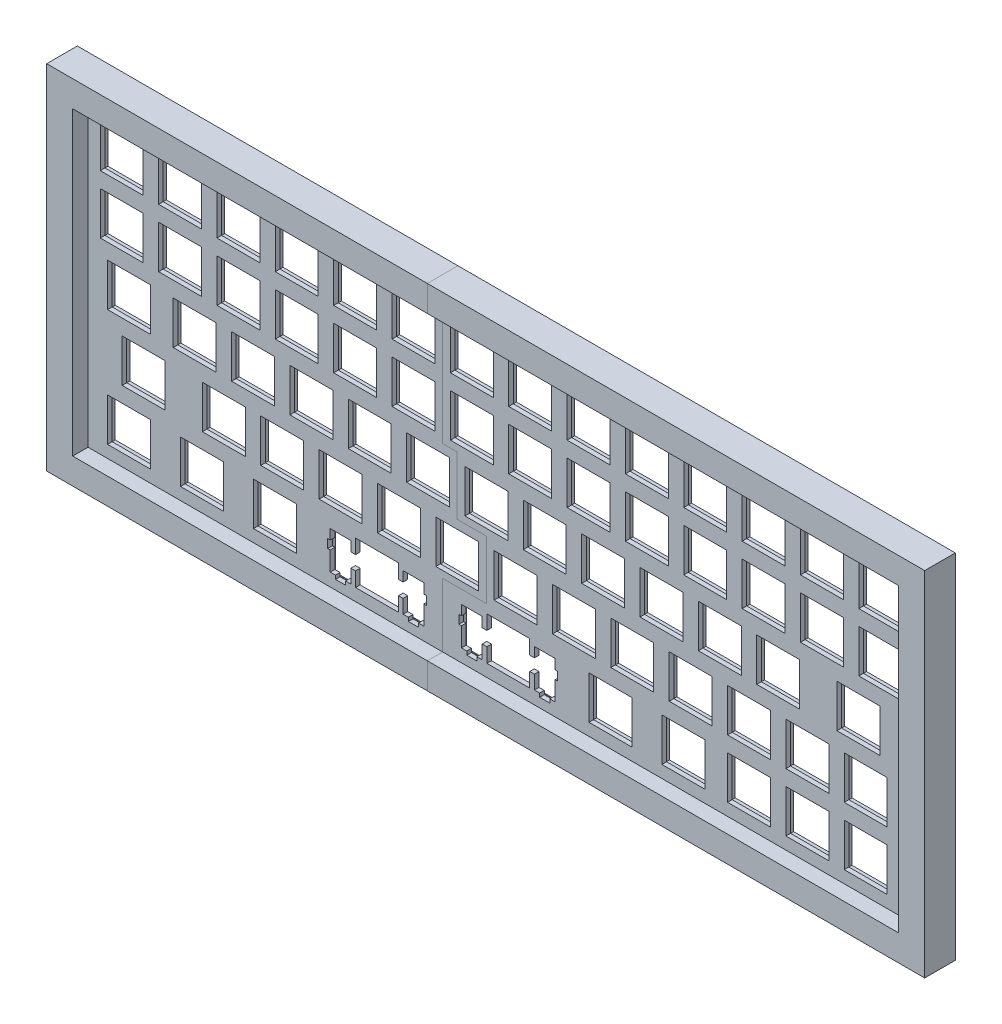
SolidWorks part; units mm, degrees
ref_plane "Front Plane" through (0, 0, 0) normal (0, 0, 1) x (1, 0, 0)
ref_plane "Top Plane" through (0, 0, 0) normal (0, 1, 0) x (1, 0, 0)
ref_plane "Right Plane" through (0, 0, 0) normal (1, 0, 0) x (0, 0, -1)
sketch "Model" plane through (0, 0, 0) normal (0, 0, 1) x (1, 0, 0)
  line L0 (0.0951, 95.5123) -> (266.8083, 95.5123)
  line L1 (266.8083, 95.5123) -> (266.8083, 0.2577)
  line L2 (266.8083, 0.2577) -> (0.0951, 0.2577)
  line L3 (0.0951, 0.2577) -> (0.0951, 95.5123)
  line L4 (85.9664, 16.7839) -> (85.9664, 12.0832)
  line L5 (85.9664, 12.0832) -> (84.4423, 12.0832)
  line L6 (84.4423, 12.0832) -> (84.4423, 15.3136)
  line L7 (84.4423, 15.3136) -> (77.6909, 15.3136)
  line L8 (77.6909, 15.3136) -> (77.6909, 12.0832)
  line L9 (77.6909, 12.0832) -> (76.8667, 12.0832)
  line L10 (76.8667, 12.0832) -> (76.8667, 9.2843)
  line L11 (76.8667, 9.2843) -> (77.6909, 9.2843)
  line L12 (77.6909, 9.2843) -> (77.6909, 3.0139)
  line L13 (77.6909, 3.0139) -> (79.416, 3.0139)
  line L14 (79.416, 3.0139) -> (79.416, 1.8136)
  line L15 (79.416, 1.8136) -> (82.7167, 1.8136)
  line L16 (82.7167, 1.8136) -> (82.7167, 3.0139)
  line L17 (82.7167, 3.0139) -> (84.4423, 3.0139)
  line L18 (84.4423, 3.0139) -> (84.4423, 7.4845)
  line L19 (84.4423, 7.4845) -> (85.9664, 7.4845)
  line L20 (85.9664, 7.4845) -> (85.9664, 2.7838)
  line L21 (85.9664, 2.7838) -> (99.9678, 2.7838)
  line L22 (99.9678, 2.7838) -> (99.9678, 7.4845)
  line L23 (99.9678, 7.4845) -> (101.4921, 7.4845)
  line L24 (101.4921, 7.4845) -> (101.4921, 3.0139)
  line L25 (101.4921, 3.0139) -> (103.2172, 3.0139)
  line L26 (103.2172, 3.0139) -> (103.2172, 1.8136)
  line L27 (103.2172, 1.8136) -> (106.5183, 1.8136)
  line L28 (106.5183, 1.8136) -> (106.5183, 3.0139)
  line L29 (106.5183, 3.0139) -> (108.2434, 3.0139)
  line L30 (108.2434, 3.0139) -> (108.2434, 9.2843)
  line L31 (108.2434, 9.2843) -> (109.0675, 9.2843)
  line L32 (109.0675, 9.2843) -> (109.0675, 12.0832)
  line L33 (109.0675, 12.0832) -> (108.2434, 12.0832)
  line L34 (108.2434, 12.0832) -> (108.2434, 15.3136)
  line L35 (108.2434, 15.3136) -> (101.4921, 15.3136)
  line L36 (101.4921, 15.3136) -> (101.4921, 12.0832)
  line L37 (101.4921, 12.0832) -> (99.9678, 12.0832)
  line L38 (99.9678, 12.0832) -> (99.9678, 16.7839)
  line L39 (99.9678, 16.7839) -> (85.9664, 16.7839)
  line L40 (128.8324, 16.7839) -> (128.8324, 12.0832)
  line L41 (128.8324, 12.0832) -> (127.3074, 12.0832)
  line L42 (127.3074, 12.0832) -> (127.3074, 15.3136)
  line L43 (127.3074, 15.3136) -> (120.557, 15.3136)
  line L44 (120.557, 15.3136) -> (120.557, 12.0832)
  line L45 (120.557, 12.0832) -> (119.731, 12.0832)
  line L46 (119.731, 12.0832) -> (119.731, 9.2843)
  line L47 (119.731, 9.2843) -> (120.557, 9.2843)
  line L48 (120.557, 9.2843) -> (120.557, 3.0139)
  line L49 (120.557, 3.0139) -> (122.2821, 3.0139)
  line L50 (122.2821, 3.0139) -> (122.2821, 1.8136)
  line L51 (122.2821, 1.8136) -> (125.5813, 1.8136)
  line L52 (125.5813, 1.8136) -> (125.5813, 3.0139)
  line L53 (125.5813, 3.0139) -> (127.3074, 3.0139)
  line L54 (127.3074, 3.0139) -> (127.3074, 7.4845)
  line L55 (127.3074, 7.4845) -> (128.8324, 7.4845)
  line L56 (128.8324, 7.4845) -> (128.8324, 2.7838)
  line L57 (128.8324, 2.7838) -> (142.8321, 2.7838)
  line L58 (142.8321, 2.7838) -> (142.8321, 7.4845)
  line L59 (142.8321, 7.4845) -> (144.3582, 7.4845)
  line L60 (144.3582, 7.4845) -> (144.3582, 3.0139)
  line L61 (144.3582, 3.0139) -> (146.0823, 3.0139)
  line L62 (146.0823, 3.0139) -> (146.0823, 1.8136)
  line L63 (146.0823, 1.8136) -> (149.3825, 1.8136)
  line L64 (149.3825, 1.8136) -> (149.3825, 3.0139)
  line L65 (149.3825, 3.0139) -> (151.1076, 3.0139)
  line L66 (151.1076, 3.0139) -> (151.1076, 9.2843)
  line L67 (151.1076, 9.2843) -> (151.9336, 9.2843)
  line L68 (151.9336, 9.2843) -> (151.9336, 12.0832)
  line L69 (151.9336, 12.0832) -> (151.1076, 12.0832)
  line L70 (151.1076, 12.0832) -> (151.1076, 15.3136)
  line L71 (151.1076, 15.3136) -> (144.3582, 15.3136)
  line L72 (144.3582, 15.3136) -> (144.3582, 12.0832)
  line L73 (144.3582, 12.0832) -> (142.8321, 12.0832)
  line L74 (142.8321, 12.0832) -> (142.8321, 16.7839)
  line L75 (142.8321, 16.7839) -> (128.8324, 16.7839)
  line L76 (5.0012, 16.7838) -> (19.0012, 16.7838)
  line L77 (19.0012, 16.7838) -> (19.0012, 2.7838)
  line L78 (19.0012, 2.7838) -> (5.0012, 2.7838)
  line L79 (5.0012, 2.7838) -> (5.0012, 16.7838)
  line L80 (28.8134, 16.7838) -> (42.8134, 16.7838)
  line L81 (42.8134, 16.7838) -> (42.8134, 2.7838)
  line L82 (42.8134, 2.7838) -> (28.8134, 2.7838)
  line L83 (28.8134, 2.7838) -> (28.8134, 16.7838)
  line L84 (52.6286, 16.7838) -> (66.6286, 16.7838)
  line L85 (66.6286, 16.7838) -> (66.6286, 2.7838)
  line L86 (66.6286, 2.7838) -> (52.6286, 2.7838)
  line L87 (52.6286, 2.7838) -> (52.6286, 16.7838)
  line L88 (162.1701, 16.7838) -> (176.1701, 16.7838)
  line L89 (176.1701, 16.7838) -> (176.1701, 2.7838)
  line L90 (176.1701, 2.7838) -> (162.1701, 2.7838)
  line L91 (162.1701, 2.7838) -> (162.1701, 16.7838)
  line L92 (185.9853, 16.7838) -> (199.9853, 16.7838)
  line L93 (199.9853, 16.7838) -> (199.9853, 2.7838)
  line L94 (199.9853, 2.7838) -> (185.9853, 2.7838)
  line L95 (185.9853, 2.7838) -> (185.9853, 16.7838)
  line L96 (207.4174, 16.7838) -> (221.4174, 16.7838)
  line L97 (221.4174, 16.7838) -> (221.4174, 2.7838)
  line L98 (221.4174, 2.7838) -> (207.4174, 2.7838)
  line L99 (207.4174, 2.7838) -> (207.4174, 16.7838)
  line L100 (226.4683, 16.7838) -> (240.4683, 16.7838)
  line L101 (240.4683, 16.7838) -> (240.4683, 2.7838)
  line L102 (240.4683, 2.7838) -> (226.4683, 2.7838)
  line L103 (226.4683, 2.7838) -> (226.4683, 16.7838)
  line L104 (245.5193, 16.7838) -> (259.5193, 16.7838)
  line L105 (259.5193, 16.7838) -> (259.5193, 2.7838)
  line L106 (259.5193, 2.7838) -> (245.5193, 2.7838)
  line L107 (245.5193, 2.7838) -> (245.5193, 16.7838)
  line L108 (9.7625, 35.8347) -> (23.7625, 35.8347)
  line L109 (23.7625, 35.8347) -> (23.7625, 21.8347)
  line L110 (23.7625, 21.8347) -> (9.7625, 21.8347)
  line L111 (9.7625, 21.8347) -> (9.7625, 35.8347)
  line L112 (35.959, 35.8347) -> (49.959, 35.8347)
  line L113 (49.959, 35.8347) -> (49.959, 21.8347)
  line L114 (49.959, 21.8347) -> (35.959, 21.8347)
  line L115 (35.959, 21.8347) -> (35.959, 35.8347)
  line L116 (55.01, 35.8347) -> (69.01, 35.8347)
  line L117 (69.01, 35.8347) -> (69.01, 21.8347)
  line L118 (69.01, 21.8347) -> (55.01, 21.8347)
  line L119 (55.01, 21.8347) -> (55.01, 35.8347)
  line L120 (74.0609, 35.8347) -> (88.0609, 35.8347)
  line L121 (88.0609, 35.8347) -> (88.0609, 21.8347)
  line L122 (88.0609, 21.8347) -> (74.0609, 21.8347)
  line L123 (74.0609, 21.8347) -> (74.0609, 35.8347)
  line L124 (93.1119, 35.8347) -> (107.1119, 35.8347)
  line L125 (107.1119, 35.8347) -> (107.1119, 21.8347)
  line L126 (107.1119, 21.8347) -> (93.1119, 21.8347)
  line L127 (93.1119, 21.8347) -> (93.1119, 35.8347)
  line L128 (112.1626, 35.8347) -> (126.1626, 35.8347)
  line L129 (126.1626, 35.8347) -> (126.1626, 21.8347)
  line L130 (126.1626, 21.8347) -> (112.1626, 21.8347)
  line L131 (112.1626, 21.8347) -> (112.1626, 35.8347)
  line L132 (131.2136, 35.8347) -> (145.2136, 35.8347)
  line L133 (145.2136, 35.8347) -> (145.2136, 21.8347)
  line L134 (145.2136, 21.8347) -> (131.2136, 21.8347)
  line L135 (131.2136, 21.8347) -> (131.2136, 35.8347)
  line L136 (150.2645, 35.8347) -> (164.2645, 35.8347)
  line L137 (164.2645, 35.8347) -> (164.2645, 21.8347)
  line L138 (164.2645, 21.8347) -> (150.2645, 21.8347)
  line L139 (150.2645, 21.8347) -> (150.2645, 35.8347)
  line L140 (169.3155, 35.8347) -> (183.3155, 35.8347)
  line L141 (183.3155, 35.8347) -> (183.3155, 21.8347)
  line L142 (183.3155, 21.8347) -> (169.3155, 21.8347)
  line L143 (169.3155, 21.8347) -> (169.3155, 35.8347)
  line L144 (188.3664, 35.8347) -> (202.3664, 35.8347)
  line L145 (202.3664, 35.8347) -> (202.3664, 21.8347)
  line L146 (202.3664, 21.8347) -> (188.3664, 21.8347)
  line L147 (188.3664, 21.8347) -> (188.3664, 35.8347)
  line L148 (207.4174, 35.8347) -> (221.4174, 35.8347)
  line L149 (221.4174, 35.8347) -> (221.4174, 21.8347)
  line L150 (221.4174, 21.8347) -> (207.4174, 21.8347)
  line L151 (207.4174, 21.8347) -> (207.4174, 35.8347)
  line L152 (226.4683, 35.8347) -> (240.4683, 35.8347)
  line L153 (240.4683, 35.8347) -> (240.4683, 21.8347)
  line L154 (240.4683, 21.8347) -> (226.4683, 21.8347)
  line L155 (226.4683, 21.8347) -> (226.4683, 35.8347)
  line L156 (245.5193, 35.8347) -> (259.5193, 35.8347)
  line L157 (259.5193, 35.8347) -> (259.5193, 21.8347)
  line L158 (259.5193, 21.8347) -> (245.5193, 21.8347)
  line L159 (245.5193, 21.8347) -> (245.5193, 35.8347)
  line L160 (5.0012, 54.8858) -> (19.0012, 54.8858)
  line L161 (19.0012, 54.8858) -> (19.0012, 40.8858)
  line L162 (19.0012, 40.8858) -> (5.0012, 40.8858)
  line L163 (5.0012, 40.8858) -> (5.0012, 54.8858)
  line L164 (26.4335, 54.8858) -> (40.4335, 54.8858)
  line L165 (40.4335, 54.8858) -> (40.4335, 40.8858)
  line L166 (40.4335, 40.8858) -> (26.4335, 40.8858)
  line L167 (26.4335, 40.8858) -> (26.4335, 54.8858)
  line L168 (45.4845, 54.8858) -> (59.4845, 54.8858)
  line L169 (59.4845, 54.8858) -> (59.4845, 40.8858)
  line L170 (59.4845, 40.8858) -> (45.4845, 40.8858)
  line L171 (45.4845, 40.8858) -> (45.4845, 54.8858)
  line L172 (64.5354, 54.8858) -> (78.5354, 54.8858)
  line L173 (78.5354, 54.8858) -> (78.5354, 40.8858)
  line L174 (78.5354, 40.8858) -> (64.5354, 40.8858)
  line L175 (64.5354, 40.8858) -> (64.5354, 54.8858)
  line L176 (83.5864, 54.8858) -> (97.5864, 54.8858)
  line L177 (97.5864, 54.8858) -> (97.5864, 40.8858)
  line L178 (97.5864, 40.8858) -> (83.5864, 40.8858)
  line L179 (83.5864, 40.8858) -> (83.5864, 54.8858)
  line L180 (102.6371, 54.8858) -> (116.6371, 54.8858)
  line L181 (116.6371, 54.8858) -> (116.6371, 40.8858)
  line L182 (116.6371, 40.8858) -> (102.6371, 40.8858)
  line L183 (102.6371, 40.8858) -> (102.6371, 54.8858)
  line L184 (121.6881, 54.8858) -> (135.6881, 54.8858)
  line L185 (135.6881, 54.8858) -> (135.6881, 40.8858)
  line L186 (135.6881, 40.8858) -> (121.6881, 40.8858)
  line L187 (121.6881, 40.8858) -> (121.6881, 54.8858)
  line L188 (140.739, 54.8858) -> (154.739, 54.8858)
  line L189 (154.739, 54.8858) -> (154.739, 40.8858)
  line L190 (154.739, 40.8858) -> (140.739, 40.8858)
  line L191 (140.739, 40.8858) -> (140.739, 54.8858)
  line L192 (159.79, 54.8858) -> (173.79, 54.8858)
  line L193 (173.79, 54.8858) -> (173.79, 40.8858)
  line L194 (173.79, 40.8858) -> (159.79, 40.8858)
  line L195 (159.79, 40.8858) -> (159.79, 54.8858)
  line L196 (178.8409, 54.8858) -> (192.8409, 54.8858)
  line L197 (192.8409, 54.8858) -> (192.8409, 40.8858)
  line L198 (192.8409, 40.8858) -> (178.8409, 40.8858)
  line L199 (178.8409, 40.8858) -> (178.8409, 54.8858)
  line L200 (197.8919, 54.8858) -> (211.8919, 54.8858)
  line L201 (211.8919, 54.8858) -> (211.8919, 40.8858)
  line L202 (211.8919, 40.8858) -> (197.8919, 40.8858)
  line L203 (197.8919, 40.8858) -> (197.8919, 54.8858)
  line L204 (216.9428, 54.8858) -> (230.9428, 54.8858)
  line L205 (230.9428, 54.8858) -> (230.9428, 40.8858)
  line L206 (230.9428, 40.8858) -> (216.9428, 40.8858)
  line L207 (216.9428, 40.8858) -> (216.9428, 54.8858)
  line L208 (243.1382, 54.8858) -> (257.1382, 54.8858)
  line L209 (257.1382, 54.8858) -> (257.1382, 40.8858)
  line L210 (257.1382, 40.8858) -> (243.1382, 40.8858)
  line L211 (243.1382, 40.8858) -> (243.1382, 54.8858)
  line L212 (2.6198, 73.9368) -> (16.6198, 73.9368)
  line L213 (16.6198, 73.9368) -> (16.6198, 59.9368)
  line L214 (16.6198, 59.9368) -> (2.6198, 59.9368)
  line L215 (2.6198, 59.9368) -> (2.6198, 73.9368)
  line L216 (21.6708, 73.9368) -> (35.6708, 73.9368)
  line L217 (35.6708, 73.9368) -> (35.6708, 59.9368)
  line L218 (35.6708, 59.9368) -> (21.6708, 59.9368)
  line L219 (21.6708, 59.9368) -> (21.6708, 73.9368)
  line L220 (40.7217, 73.9368) -> (54.7217, 73.9368)
  line L221 (54.7217, 73.9368) -> (54.7217, 59.9368)
  line L222 (54.7217, 59.9368) -> (40.7217, 59.9368)
  line L223 (40.7217, 59.9368) -> (40.7217, 73.9368)
  line L224 (59.7727, 73.9368) -> (73.7727, 73.9368)
  line L225 (73.7727, 73.9368) -> (73.7727, 59.9368)
  line L226 (73.7727, 59.9368) -> (59.7727, 59.9368)
  line L227 (59.7727, 59.9368) -> (59.7727, 73.9368)
  line L228 (78.8236, 73.9368) -> (92.8236, 73.9368)
  line L229 (92.8236, 73.9368) -> (92.8236, 59.9368)
  line L230 (92.8236, 59.9368) -> (78.8236, 59.9368)
  line L231 (78.8236, 59.9368) -> (78.8236, 73.9368)
  line L232 (97.8732, 73.9368) -> (111.8732, 73.9368)
  line L233 (111.8732, 73.9368) -> (111.8732, 59.9368)
  line L234 (111.8732, 59.9368) -> (97.8732, 59.9368)
  line L235 (97.8732, 59.9368) -> (97.8732, 73.9368)
  line L236 (116.9238, 73.9368) -> (130.9238, 73.9368)
  line L237 (130.9238, 73.9368) -> (130.9238, 59.9368)
  line L238 (130.9238, 59.9368) -> (116.9238, 59.9368)
  line L239 (116.9238, 59.9368) -> (116.9238, 73.9368)
  line L240 (135.9768, 73.9368) -> (149.9768, 73.9368)
  line L241 (149.9768, 73.9368) -> (149.9768, 59.9368)
  line L242 (149.9768, 59.9368) -> (135.9768, 59.9368)
  line L243 (135.9768, 59.9368) -> (135.9768, 73.9368)
  line L244 (155.0278, 73.9368) -> (169.0278, 73.9368)
  line L245 (169.0278, 73.9368) -> (169.0278, 59.9368)
  line L246 (169.0278, 59.9368) -> (155.0278, 59.9368)
  line L247 (155.0278, 59.9368) -> (155.0278, 73.9368)
  line L248 (174.0787, 73.9368) -> (188.0787, 73.9368)
  line L249 (188.0787, 73.9368) -> (188.0787, 59.9368)
  line L250 (188.0787, 59.9368) -> (174.0787, 59.9368)
  line L251 (174.0787, 59.9368) -> (174.0787, 73.9368)
  line L252 (193.1297, 73.9368) -> (207.1297, 73.9368)
  line L253 (207.1297, 73.9368) -> (207.1297, 59.9368)
  line L254 (207.1297, 59.9368) -> (193.1297, 59.9368)
  line L255 (193.1297, 59.9368) -> (193.1297, 73.9368)
  line L256 (212.1806, 73.9368) -> (226.1806, 73.9368)
  line L257 (226.1806, 73.9368) -> (226.1806, 59.9368)
  line L258 (226.1806, 59.9368) -> (212.1806, 59.9368)
  line L259 (212.1806, 59.9368) -> (212.1806, 73.9368)
  line L260 (231.2316, 73.9368) -> (245.2316, 73.9368)
  line L261 (245.2316, 73.9368) -> (245.2316, 59.9368)
  line L262 (245.2316, 59.9368) -> (231.2316, 59.9368)
  line L263 (231.2316, 59.9368) -> (231.2316, 73.9368)
  line L264 (250.2825, 73.9368) -> (264.2825, 73.9368)
  line L265 (264.2825, 73.9368) -> (264.2825, 59.9368)
  line L266 (264.2825, 59.9368) -> (250.2825, 59.9368)
  line L267 (250.2825, 59.9368) -> (250.2825, 73.9368)
  line L268 (2.6198, 92.9877) -> (16.6198, 92.9877)
  line L269 (16.6198, 92.9877) -> (16.6198, 78.9877)
  line L270 (16.6198, 78.9877) -> (2.6198, 78.9877)
  line L271 (2.6198, 78.9877) -> (2.6198, 92.9877)
  line L272 (21.6708, 92.9877) -> (35.6708, 92.9877)
  line L273 (35.6708, 92.9877) -> (35.6708, 78.9877)
  line L274 (35.6708, 78.9877) -> (21.6708, 78.9877)
  line L275 (21.6708, 78.9877) -> (21.6708, 92.9877)
  line L276 (40.7217, 92.9877) -> (54.7217, 92.9877)
  line L277 (54.7217, 92.9877) -> (54.7217, 78.9877)
  line L278 (54.7217, 78.9877) -> (40.7217, 78.9877)
  line L279 (40.7217, 78.9877) -> (40.7217, 92.9877)
  line L280 (59.7727, 92.9877) -> (73.7727, 92.9877)
  line L281 (73.7727, 92.9877) -> (73.7727, 78.9877)
  line L282 (73.7727, 78.9877) -> (59.7727, 78.9877)
  line L283 (59.7727, 78.9877) -> (59.7727, 92.9877)
  line L284 (78.8236, 92.9877) -> (92.8236, 92.9877)
  line L285 (92.8236, 92.9877) -> (92.8236, 78.9877)
  line L286 (92.8236, 78.9877) -> (78.8236, 78.9877)
  line L287 (78.8236, 78.9877) -> (78.8236, 92.9877)
  line L288 (97.8732, 92.9877) -> (111.8732, 92.9877)
  line L289 (111.8732, 92.9877) -> (111.8732, 78.9877)
  line L290 (111.8732, 78.9877) -> (97.8732, 78.9877)
  line L291 (97.8732, 78.9877) -> (97.8732, 92.9877)
  line L292 (116.9238, 92.9877) -> (130.9238, 92.9877)
  line L293 (130.9238, 92.9877) -> (130.9238, 78.9877)
  line L294 (130.9238, 78.9877) -> (116.9238, 78.9877)
  line L295 (116.9238, 78.9877) -> (116.9238, 92.9877)
  line L296 (135.9768, 92.9877) -> (149.9768, 92.9877)
  line L297 (149.9768, 92.9877) -> (149.9768, 78.9877)
  line L298 (149.9768, 78.9877) -> (135.9768, 78.9877)
  line L299 (135.9768, 78.9877) -> (135.9768, 92.9877)
  line L300 (155.0278, 92.9877) -> (169.0278, 92.9877)
  line L301 (169.0278, 92.9877) -> (169.0278, 78.9877)
  line L302 (169.0278, 78.9877) -> (155.0278, 78.9877)
  line L303 (155.0278, 78.9877) -> (155.0278, 92.9877)
  line L304 (174.0787, 92.9877) -> (188.0787, 92.9877)
  line L305 (188.0787, 92.9877) -> (188.0787, 78.9877)
  line L306 (188.0787, 78.9877) -> (174.0787, 78.9877)
  line L307 (174.0787, 78.9877) -> (174.0787, 92.9877)
  line L308 (193.1297, 92.9877) -> (207.1297, 92.9877)
  line L309 (207.1297, 92.9877) -> (207.1297, 78.9877)
  line L310 (207.1297, 78.9877) -> (193.1297, 78.9877)
  line L311 (193.1297, 78.9877) -> (193.1297, 92.9877)
  line L312 (212.1806, 92.9877) -> (226.1806, 92.9877)
  line L313 (226.1806, 92.9877) -> (226.1806, 78.9877)
  line L314 (226.1806, 78.9877) -> (212.1806, 78.9877)
  line L315 (212.1806, 78.9877) -> (212.1806, 92.9877)
  line L316 (231.2316, 92.9877) -> (245.2316, 92.9877)
  line L317 (245.2316, 92.9877) -> (245.2316, 78.9877)
  line L318 (245.2316, 78.9877) -> (231.2316, 78.9877)
  line L319 (231.2316, 78.9877) -> (231.2316, 92.9877)
  line L320 (250.2825, 92.9877) -> (264.2825, 92.9877)
  line L321 (264.2825, 92.9877) -> (264.2825, 78.9877)
  line L322 (264.2825, 78.9877) -> (250.2825, 78.9877)
  line L323 (250.2825, 78.9877) -> (250.2825, 92.9877)
  dimension "D1" = 14
  dimension "D2" = 13.9997
  dimension "D3" = 5.051
  dimension "D4" = 5.051
extrude "Boss-Extrude1" add sketch "Model" along normal blind 1.5
sketch "Sketch2" plane through (0, 0, 1.5) normal (0, 0, 1) x (1, 0, 0)
  line L8 (266.8083, 0.2577) -> (266.8083, 95.5123)
  line L9 (266.8083, 95.5123) -> (0.0951, 95.5123)
  line L10 (0.0951, 95.5123) -> (0.0951, 0.2577)
  line L11 (0.0951, 0.2577) -> (266.8083, 0.2577)
  line L12 (-1.3749, 96.9823) -> (-1.3749, -1.2123)
  line L13 (-1.3749, -1.2123) -> (268.2783, -1.2123)
  line L14 (268.2783, -1.2123) -> (268.2783, 96.9823)
  line L15 (268.2783, 96.9823) -> (-1.3749, 96.9823)
  line L16 (-1.3749, 96.9823) -> (-1.3749, -1.2123)
  line L17 (-1.3749, -1.2123) -> (268.2783, -1.2123)
  line L18 (268.2783, -1.2123) -> (268.2783, 96.9823)
  line L19 (268.2783, 96.9823) -> (-1.3749, 96.9823)
  dimension "D1" = 1.47
extrude "Boss-Extrude3" add sketch "Sketch2" against normal blind 1.5 contours L18 L19 L16 L17 L11 L10 L9 L8 region at (133.4517, 96.6953, 1.5)
sketch "Sketch3" plane through (0, 0, 1.5) normal (0, 0, 1) x (1, 0, 0)
  line L0 (168.3155, 36.8347) -> (168.3155, 20.8347)
  line L1 (184.3155, 36.8347) -> (168.3155, 36.8347)
  line L2 (184.3155, 20.8347) -> (184.3155, 36.8347)
  line L3 (168.3155, 20.8347) -> (184.3155, 20.8347)
  line L4 (177.1701, 1.7838) -> (177.1701, 17.7838)
  line L5 (161.1701, 17.7838) -> (161.1701, 1.7838)
  line L6 (161.1701, 1.7838) -> (177.1701, 1.7838)
  line L7 (177.1701, 17.7838) -> (161.1701, 17.7838)
  line L8 (165.2645, 20.8347) -> (165.2645, 36.8347)
  line L9 (149.2645, 20.8347) -> (165.2645, 20.8347)
  line L10 (165.2645, 36.8347) -> (149.2645, 36.8347)
  line L11 (20.6708, 77.9877) -> (36.6708, 77.9877)
  line L12 (36.6708, 77.9877) -> (36.6708, 93.9877)
  line L13 (36.6708, 93.9877) -> (20.6708, 93.9877)
  line L14 (20.6708, 93.9877) -> (20.6708, 77.9877)
  line L15 (20.6708, 77.9877) -> (36.6708, 77.9877)
  line L16 (36.6708, 77.9877) -> (36.6708, 93.9877)
  line L17 (36.6708, 93.9877) -> (20.6708, 93.9877)
  line L18 (20.6708, 93.9877) -> (20.6708, 77.9877)
  line L23 (134.9768, 77.9877) -> (150.9768, 77.9877)
  line L24 (150.9768, 77.9877) -> (150.9768, 93.9877)
  line L25 (265.2825, 93.9877) -> (249.2825, 93.9877)
  line L26 (96.8732, 77.9877) -> (112.8732, 77.9877)
  line L27 (96.8732, 93.9877) -> (96.8732, 77.9877)
  line L28 (112.8732, 93.9877) -> (96.8732, 93.9877)
  line L29 (112.8732, 77.9877) -> (112.8732, 93.9877)
  line L30 (96.8732, 77.9877) -> (112.8732, 77.9877)
  line L38 (96.8732, 93.9877) -> (96.8732, 77.9877)
  line L39 (112.8732, 93.9877) -> (96.8732, 93.9877)
  line L40 (112.8732, 77.9877) -> (112.8732, 93.9877)
  line L41 (249.2825, 93.9877) -> (249.2825, 77.9877)
  line L42 (1.6198, 93.9877) -> (1.6198, 77.9877)
  line L43 (1.6198, 77.9877) -> (17.6198, 77.9877)
  line L44 (17.6198, 77.9877) -> (17.6198, 93.9877)
  line L45 (17.6198, 93.9877) -> (1.6198, 93.9877)
  line L46 (1.6198, 93.9877) -> (1.6198, 77.9877)
  line L47 (1.6198, 77.9877) -> (17.6198, 77.9877)
  line L48 (17.6198, 77.9877) -> (17.6198, 93.9877)
  line L49 (17.6198, 93.9877) -> (1.6198, 93.9877)
  line L50 (249.2825, 77.9877) -> (265.2825, 77.9877)
  line L51 (265.2825, 77.9877) -> (265.2825, 93.9877)
  line L53 (115.9238, 93.9877) -> (115.9238, 77.9877)
  line L54 (115.9238, 77.9877) -> (131.9238, 77.9877)
  line L55 (131.9238, 77.9877) -> (131.9238, 93.9877)
  line L56 (131.9238, 93.9877) -> (115.9238, 93.9877)
  line L57 (115.9238, 93.9877) -> (115.9238, 77.9877)
  line L58 (115.9238, 77.9877) -> (131.9238, 77.9877)
  line L59 (131.9238, 77.9877) -> (131.9238, 93.9877)
  line L60 (131.9238, 93.9877) -> (115.9238, 93.9877)
  line L61 (265.2825, 93.9877) -> (249.2825, 93.9877)
  line L62 (154.0278, 77.9877) -> (170.0278, 77.9877)
  line L63 (134.9768, 93.9877) -> (134.9768, 77.9877)
  line L64 (150.9768, 93.9877) -> (134.9768, 93.9877)
  line L65 (134.9768, 77.9877) -> (150.9768, 77.9877)
  line L66 (150.9768, 77.9877) -> (150.9768, 93.9877)
  line L67 (39.7217, 77.9877) -> (55.7217, 77.9877)
  line L68 (55.7217, 77.9877) -> (55.7217, 93.9877)
  line L69 (39.7217, 93.9877) -> (39.7217, 77.9877)
  line L70 (55.7217, 93.9877) -> (39.7217, 93.9877)
  line L71 (39.7217, 77.9877) -> (55.7217, 77.9877)
  line L72 (55.7217, 77.9877) -> (55.7217, 93.9877)
  line L73 (39.7217, 93.9877) -> (39.7217, 77.9877)
  line L74 (55.7217, 93.9877) -> (39.7217, 93.9877)
  line L75 (134.9768, 93.9877) -> (134.9768, 77.9877)
  line L76 (150.9768, 93.9877) -> (134.9768, 93.9877)
  line L77 (154.0278, 93.9877) -> (154.0278, 77.9877)
  line L78 (170.0278, 93.9877) -> (154.0278, 93.9877)
  line L79 (170.0278, 77.9877) -> (170.0278, 93.9877)
  line L80 (154.0278, 77.9877) -> (170.0278, 77.9877)
  line L81 (154.0278, 93.9877) -> (154.0278, 77.9877)
  line L82 (170.0278, 93.9877) -> (154.0278, 93.9877)
  line L83 (170.0278, 77.9877) -> (170.0278, 93.9877)
  line L84 (249.2825, 93.9877) -> (249.2825, 77.9877)
  line L85 (58.7727, 93.9877) -> (58.7727, 77.9877)
  line L86 (58.7727, 77.9877) -> (74.7727, 77.9877)
  line L87 (74.7727, 77.9877) -> (74.7727, 93.9877)
  line L88 (74.7727, 93.9877) -> (58.7727, 93.9877)
  line L89 (58.7727, 93.9877) -> (58.7727, 77.9877)
  line L90 (58.7727, 77.9877) -> (74.7727, 77.9877)
  line L91 (74.7727, 77.9877) -> (74.7727, 93.9877)
  line L92 (74.7727, 93.9877) -> (58.7727, 93.9877)
  line L93 (249.2825, 77.9877) -> (265.2825, 77.9877)
  line L94 (265.2825, 77.9877) -> (265.2825, 93.9877)
  line L95 (149.2645, 36.8347) -> (149.2645, 20.8347)
  line L96 (130.2136, 20.8347) -> (146.2136, 20.8347)
  line L97 (146.2136, 36.8347) -> (130.2136, 36.8347)
  line L98 (134.9768, 74.9368) -> (134.9768, 58.9368)
  line L99 (134.9768, 58.9368) -> (150.9768, 58.9368)
  line L100 (150.9768, 58.9368) -> (150.9768, 74.9368)
  line L101 (150.9768, 74.9368) -> (134.9768, 74.9368)
  line L102 (173.0787, 93.9877) -> (173.0787, 77.9877)
  line L103 (173.0787, 77.9877) -> (189.0787, 77.9877)
  line L104 (189.0787, 77.9877) -> (189.0787, 93.9877)
  line L105 (189.0787, 93.9877) -> (173.0787, 93.9877)
  line L106 (173.0787, 93.9877) -> (173.0787, 77.9877)
  line L107 (173.0787, 77.9877) -> (189.0787, 77.9877)
  line L108 (189.0787, 77.9877) -> (189.0787, 93.9877)
  line L109 (189.0787, 93.9877) -> (173.0787, 93.9877)
  line L110 (134.9768, 74.9368) -> (134.9768, 58.9368)
  line L111 (134.9768, 58.9368) -> (150.9768, 58.9368)
  line L112 (150.9768, 58.9368) -> (150.9768, 74.9368)
  line L113 (249.2825, 58.9368) -> (265.2825, 58.9368)
  line L114 (265.2825, 58.9368) -> (265.2825, 74.9368)
  line L115 (249.2825, 74.9368) -> (249.2825, 58.9368)
  line L116 (265.2825, 74.9368) -> (249.2825, 74.9368)
  line L117 (249.2825, 58.9368) -> (265.2825, 58.9368)
  line L118 (265.2825, 58.9368) -> (265.2825, 74.9368)
  line L119 (249.2825, 74.9368) -> (249.2825, 58.9368)
  line L120 (192.1297, 77.9877) -> (208.1297, 77.9877)
  line L121 (192.1297, 93.9877) -> (192.1297, 77.9877)
  line L122 (208.1297, 77.9877) -> (208.1297, 93.9877)
  line L123 (208.1297, 93.9877) -> (192.1297, 93.9877)
  line L124 (192.1297, 77.9877) -> (208.1297, 77.9877)
  line L125 (192.1297, 93.9877) -> (192.1297, 77.9877)
  line L126 (208.1297, 77.9877) -> (208.1297, 93.9877)
  line L127 (77.8236, 77.9877) -> (93.8236, 77.9877)
  line L128 (93.8236, 77.9877) -> (93.8236, 93.9877)
  line L129 (77.8236, 93.9877) -> (77.8236, 77.9877)
  line L130 (93.8236, 93.9877) -> (77.8236, 93.9877)
  line L131 (77.8236, 77.9877) -> (93.8236, 77.9877)
  line L132 (93.8236, 77.9877) -> (93.8236, 93.9877)
  line L133 (77.8236, 93.9877) -> (77.8236, 77.9877)
  line L134 (93.8236, 93.9877) -> (77.8236, 93.9877)
  line L135 (208.1297, 93.9877) -> (192.1297, 93.9877)
  line L136 (265.2825, 74.9368) -> (249.2825, 74.9368)
  line L137 (150.9768, 74.9368) -> (134.9768, 74.9368)
  line L138 (58.7727, 74.9368) -> (58.7727, 58.9368)
  line L139 (58.7727, 58.9368) -> (74.7727, 58.9368)
  line L140 (74.7727, 58.9368) -> (74.7727, 74.9368)
  line L141 (96.8732, 58.9368) -> (112.8732, 58.9368)
  line L142 (112.8732, 58.9368) -> (112.8732, 74.9368)
  line L143 (96.8732, 74.9368) -> (96.8732, 58.9368)
  line L144 (112.8732, 74.9368) -> (96.8732, 74.9368)
  line L145 (96.8732, 58.9368) -> (112.8732, 58.9368)
  line L146 (211.1806, 77.9877) -> (227.1806, 77.9877)
  line L147 (227.1806, 77.9877) -> (227.1806, 93.9877)
  line L148 (211.1806, 93.9877) -> (211.1806, 77.9877)
  line L149 (227.1806, 93.9877) -> (211.1806, 93.9877)
  line L150 (211.1806, 77.9877) -> (227.1806, 77.9877)
  line L151 (227.1806, 77.9877) -> (227.1806, 93.9877)
  line L152 (211.1806, 93.9877) -> (211.1806, 77.9877)
  line L153 (227.1806, 93.9877) -> (211.1806, 93.9877)
  line L154 (112.8732, 58.9368) -> (112.8732, 74.9368)
  line L155 (230.2316, 74.9368) -> (230.2316, 58.9368)
  line L156 (230.2316, 58.9368) -> (246.2316, 58.9368)
  line L157 (246.2316, 58.9368) -> (246.2316, 74.9368)
  line L158 (246.2316, 74.9368) -> (230.2316, 74.9368)
  line L159 (230.2316, 74.9368) -> (230.2316, 58.9368)
  line L160 (96.8732, 74.9368) -> (96.8732, 58.9368)
  line L161 (115.9238, 58.9368) -> (131.9238, 58.9368)
  line L162 (131.9238, 58.9368) -> (131.9238, 74.9368)
  line L163 (115.9238, 74.9368) -> (115.9238, 58.9368)
  line L164 (230.2316, 77.9877) -> (246.2316, 77.9877)
  line L165 (246.2316, 77.9877) -> (246.2316, 93.9877)
  line L166 (230.2316, 93.9877) -> (230.2316, 77.9877)
  line L167 (246.2316, 93.9877) -> (230.2316, 93.9877)
  line L168 (230.2316, 77.9877) -> (246.2316, 77.9877)
  line L169 (246.2316, 77.9877) -> (246.2316, 93.9877)
  line L170 (230.2316, 93.9877) -> (230.2316, 77.9877)
  line L171 (246.2316, 93.9877) -> (230.2316, 93.9877)
  line L172 (131.9238, 74.9368) -> (115.9238, 74.9368)
  line L173 (115.9238, 58.9368) -> (131.9238, 58.9368)
  line L174 (230.2316, 58.9368) -> (246.2316, 58.9368)
  line L175 (246.2316, 58.9368) -> (246.2316, 74.9368)
  line L176 (246.2316, 74.9368) -> (230.2316, 74.9368)
  line L177 (131.9238, 58.9368) -> (131.9238, 74.9368)
  line L178 (115.9238, 74.9368) -> (115.9238, 58.9368)
  line L179 (131.9238, 74.9368) -> (115.9238, 74.9368)
  line L180 (112.8732, 74.9368) -> (96.8732, 74.9368)
  line L181 (74.7727, 74.9368) -> (58.7727, 74.9368)
  line L182 (58.7727, 74.9368) -> (58.7727, 58.9368)
  line L183 (58.7727, 58.9368) -> (74.7727, 58.9368)
  line L184 (74.7727, 58.9368) -> (74.7727, 74.9368)
  line L185 (74.7727, 74.9368) -> (58.7727, 74.9368)
  line L186 (155.739, 39.8858) -> (155.739, 55.8858)
  line L187 (192.1297, 74.9368) -> (192.1297, 58.9368)
  line L188 (192.1297, 58.9368) -> (208.1297, 58.9368)
  line L189 (208.1297, 58.9368) -> (208.1297, 74.9368)
  line L190 (208.1297, 74.9368) -> (192.1297, 74.9368)
  line L191 (192.1297, 74.9368) -> (192.1297, 58.9368)
  line L192 (192.1297, 58.9368) -> (208.1297, 58.9368)
  line L193 (208.1297, 58.9368) -> (208.1297, 74.9368)
  line L194 (208.1297, 74.9368) -> (192.1297, 74.9368)
  line L199 (93.8236, 74.9368) -> (77.8236, 74.9368)
  line L200 (77.8236, 74.9368) -> (77.8236, 58.9368)
  line L201 (77.8236, 58.9368) -> (93.8236, 58.9368)
  line L202 (93.8236, 58.9368) -> (93.8236, 74.9368)
  line L203 (93.8236, 74.9368) -> (77.8236, 74.9368)
  line L204 (77.8236, 74.9368) -> (77.8236, 58.9368)
  line L205 (211.1806, 58.9368) -> (227.1806, 58.9368)
  line L206 (227.1806, 58.9368) -> (227.1806, 74.9368)
  line L207 (211.1806, 74.9368) -> (211.1806, 58.9368)
  line L208 (227.1806, 74.9368) -> (211.1806, 74.9368)
  line L209 (211.1806, 58.9368) -> (227.1806, 58.9368)
  line L210 (227.1806, 58.9368) -> (227.1806, 74.9368)
  line L211 (211.1806, 74.9368) -> (211.1806, 58.9368)
  line L212 (227.1806, 74.9368) -> (211.1806, 74.9368)
  line L213 (77.8236, 58.9368) -> (93.8236, 58.9368)
  line L214 (93.8236, 58.9368) -> (93.8236, 74.9368)
  line L215 (139.739, 39.8858) -> (155.739, 39.8858)
  line L216 (139.739, 55.8858) -> (139.739, 39.8858)
  line L217 (39.7217, 58.9368) -> (55.7217, 58.9368)
  line L218 (55.7217, 58.9368) -> (55.7217, 74.9368)
  line L219 (55.7217, 74.9368) -> (39.7217, 74.9368)
  line L220 (39.7217, 74.9368) -> (39.7217, 58.9368)
  line L221 (39.7217, 58.9368) -> (55.7217, 58.9368)
  line L222 (55.7217, 58.9368) -> (55.7217, 74.9368)
  line L223 (173.0787, 58.9368) -> (189.0787, 58.9368)
  line L224 (189.0787, 58.9368) -> (189.0787, 74.9368)
  line L225 (173.0787, 74.9368) -> (173.0787, 58.9368)
  line L226 (189.0787, 74.9368) -> (173.0787, 74.9368)
  line L227 (173.0787, 58.9368) -> (189.0787, 58.9368)
  line L228 (189.0787, 58.9368) -> (189.0787, 74.9368)
  line L229 (173.0787, 74.9368) -> (173.0787, 58.9368)
  line L230 (189.0787, 74.9368) -> (173.0787, 74.9368)
  line L231 (55.7217, 74.9368) -> (39.7217, 74.9368)
  line L232 (39.7217, 74.9368) -> (39.7217, 58.9368)
  line L233 (155.739, 55.8858) -> (139.739, 55.8858)
  line L234 (155.739, 39.8858) -> (155.739, 55.8858)
  line L235 (139.739, 39.8858) -> (155.739, 39.8858)
  line L236 (139.739, 55.8858) -> (139.739, 39.8858)
  line L237 (155.739, 55.8858) -> (139.739, 55.8858)
  line L238 (146.2136, 20.8347) -> (146.2136, 36.8347)
  line L239 (130.2136, 36.8347) -> (130.2136, 20.8347)
  line L240 (127.1626, 20.8347) -> (127.1626, 36.8347)
  line L241 (170.0278, 74.9368) -> (154.0278, 74.9368)
  line L242 (154.0278, 74.9368) -> (154.0278, 58.9368)
  line L243 (154.0278, 58.9368) -> (170.0278, 58.9368)
  line L244 (170.0278, 58.9368) -> (170.0278, 74.9368)
  line L245 (170.0278, 74.9368) -> (154.0278, 74.9368)
  line L246 (154.0278, 74.9368) -> (154.0278, 58.9368)
  line L247 (154.0278, 58.9368) -> (170.0278, 58.9368)
  line L248 (170.0278, 58.9368) -> (170.0278, 74.9368)
  line L249 (111.1626, 36.8347) -> (111.1626, 20.8347)
  line L250 (177.8409, 39.8858) -> (193.8409, 39.8858)
  line L251 (193.8409, 39.8858) -> (193.8409, 55.8858)
  line L252 (177.8409, 55.8858) -> (177.8409, 39.8858)
  line L253 (193.8409, 55.8858) -> (177.8409, 55.8858)
  line L254 (20.6708, 58.9368) -> (36.6708, 58.9368)
  line L255 (36.6708, 58.9368) -> (36.6708, 74.9368)
  line L256 (36.6708, 74.9368) -> (20.6708, 74.9368)
  line L257 (20.6708, 74.9368) -> (20.6708, 58.9368)
  line L258 (20.6708, 58.9368) -> (36.6708, 58.9368)
  line L259 (36.6708, 58.9368) -> (36.6708, 74.9368)
  line L260 (36.6708, 74.9368) -> (20.6708, 74.9368)
  line L261 (20.6708, 74.9368) -> (20.6708, 58.9368)
  line L262 (177.8409, 39.8858) -> (193.8409, 39.8858)
  line L263 (193.8409, 39.8858) -> (193.8409, 55.8858)
  line L264 (158.79, 39.8858) -> (174.79, 39.8858)
  line L265 (174.79, 39.8858) -> (174.79, 55.8858)
  line L266 (158.79, 55.8858) -> (158.79, 39.8858)
  line L267 (174.79, 55.8858) -> (158.79, 55.8858)
  line L268 (158.79, 39.8858) -> (174.79, 39.8858)
  line L269 (174.79, 39.8858) -> (174.79, 55.8858)
  line L270 (158.79, 55.8858) -> (158.79, 39.8858)
  line L271 (174.79, 55.8858) -> (158.79, 55.8858)
  line L272 (17.6198, 74.9368) -> (1.6198, 74.9368)
  line L273 (1.6198, 74.9368) -> (1.6198, 58.9368)
  line L274 (1.6198, 58.9368) -> (17.6198, 58.9368)
  line L275 (17.6198, 58.9368) -> (17.6198, 74.9368)
  line L276 (17.6198, 74.9368) -> (1.6198, 74.9368)
  line L277 (1.6198, 74.9368) -> (1.6198, 58.9368)
  line L278 (1.6198, 58.9368) -> (17.6198, 58.9368)
  line L279 (17.6198, 58.9368) -> (17.6198, 74.9368)
  line L280 (177.8409, 55.8858) -> (177.8409, 39.8858)
  line L281 (193.8409, 55.8858) -> (177.8409, 55.8858)
  line L282 (127.1626, 36.8347) -> (111.1626, 36.8347)
  line L283 (111.1626, 20.8347) -> (127.1626, 20.8347)
  line L284 (108.1119, 36.8347) -> (92.1119, 36.8347)
  line L285 (92.1119, 20.8347) -> (108.1119, 20.8347)
  line L286 (108.1119, 20.8347) -> (108.1119, 36.8347)
  line L287 (92.1119, 36.8347) -> (92.1119, 20.8347)
  line L288 (89.0609, 20.8347) -> (89.0609, 36.8347)
  line L289 (73.0609, 36.8347) -> (73.0609, 20.8347)
  line L290 (73.0609, 20.8347) -> (89.0609, 20.8347)
  line L291 (89.0609, 36.8347) -> (73.0609, 36.8347)
  line L292 (196.8919, 55.8858) -> (196.8919, 39.8858)
  line L293 (4.0012, 39.8858) -> (20.0012, 39.8858)
  line L294 (20.0012, 39.8858) -> (20.0012, 55.8858)
  line L295 (4.0012, 55.8858) -> (4.0012, 39.8858)
  line L296 (20.0012, 55.8858) -> (4.0012, 55.8858)
  line L297 (4.0012, 39.8858) -> (20.0012, 39.8858)
  line L298 (20.0012, 39.8858) -> (20.0012, 55.8858)
  line L299 (4.0012, 55.8858) -> (4.0012, 39.8858)
  line L300 (20.0012, 55.8858) -> (4.0012, 55.8858)
  line L301 (212.8919, 39.8858) -> (212.8919, 55.8858)
  line L302 (196.8919, 39.8858) -> (212.8919, 39.8858)
  line L303 (212.8919, 55.8858) -> (196.8919, 55.8858)
  line L304 (196.8919, 55.8858) -> (196.8919, 39.8858)
  line L305 (212.8919, 39.8858) -> (212.8919, 55.8858)
  line L306 (196.8919, 39.8858) -> (212.8919, 39.8858)
  line L307 (212.8919, 55.8858) -> (196.8919, 55.8858)
  line L308 (70.01, 36.8347) -> (54.01, 36.8347)
  line L309 (54.01, 20.8347) -> (70.01, 20.8347)
  line L310 (70.01, 20.8347) -> (70.01, 36.8347)
  line L311 (25.4335, 55.8858) -> (25.4335, 39.8858)
  line L312 (25.4335, 39.8858) -> (41.4335, 39.8858)
  line L313 (41.4335, 39.8858) -> (41.4335, 55.8858)
  line L314 (41.4335, 55.8858) -> (25.4335, 55.8858)
  line L315 (25.4335, 55.8858) -> (25.4335, 39.8858)
  line L316 (25.4335, 39.8858) -> (41.4335, 39.8858)
  line L317 (41.4335, 39.8858) -> (41.4335, 55.8858)
  line L318 (41.4335, 55.8858) -> (25.4335, 55.8858)
  line L319 (54.01, 36.8347) -> (54.01, 20.8347)
  line L320 (50.959, 20.8347) -> (50.959, 36.8347)
  line L321 (50.959, 36.8347) -> (34.959, 36.8347)
  line L322 (34.959, 36.8347) -> (34.959, 20.8347)
  line L323 (34.959, 20.8347) -> (50.959, 20.8347)
  line L324 (51.6286, 17.7838) -> (51.6286, 1.7838)
  line L325 (67.6286, 17.7838) -> (51.6286, 17.7838)
  line L326 (231.9428, 55.8858) -> (215.9428, 55.8858)
  line L327 (215.9428, 55.8858) -> (215.9428, 39.8858)
  line L328 (231.9428, 39.8858) -> (231.9428, 55.8858)
  line L329 (215.9428, 39.8858) -> (231.9428, 39.8858)
  line L330 (60.4845, 39.8858) -> (60.4845, 55.8858)
  line L331 (44.4845, 39.8858) -> (60.4845, 39.8858)
  line L332 (44.4845, 55.8858) -> (44.4845, 39.8858)
  line L333 (60.4845, 55.8858) -> (44.4845, 55.8858)
  line L334 (60.4845, 39.8858) -> (60.4845, 55.8858)
  line L335 (44.4845, 39.8858) -> (60.4845, 39.8858)
  line L336 (44.4845, 55.8858) -> (44.4845, 39.8858)
  line L337 (60.4845, 55.8858) -> (44.4845, 55.8858)
  line L338 (231.9428, 55.8858) -> (215.9428, 55.8858)
  line L339 (215.9428, 55.8858) -> (215.9428, 39.8858)
  line L340 (231.9428, 39.8858) -> (231.9428, 55.8858)
  line L341 (215.9428, 39.8858) -> (231.9428, 39.8858)
  line L342 (51.6286, 1.7838) -> (67.6286, 1.7838)
  line L343 (67.6286, 1.7838) -> (67.6286, 17.7838)
  line L344 (43.8134, 17.7838) -> (27.8134, 17.7838)
  line L345 (27.8134, 17.7838) -> (27.8134, 1.7838)
  line L346 (27.8134, 1.7838) -> (43.8134, 1.7838)
  line L347 (43.8134, 1.7838) -> (43.8134, 17.7838)
  line L348 (63.5354, 55.8858) -> (63.5354, 39.8858)
  line L349 (63.5354, 39.8858) -> (79.5354, 39.8858)
  line L350 (79.5354, 39.8858) -> (79.5354, 55.8858)
  line L351 (79.5354, 55.8858) -> (63.5354, 55.8858)
  line L352 (63.5354, 55.8858) -> (63.5354, 39.8858)
  line L353 (63.5354, 39.8858) -> (79.5354, 39.8858)
  line L354 (79.5354, 39.8858) -> (79.5354, 55.8858)
  line L355 (79.5354, 55.8858) -> (63.5354, 55.8858)
  line L356 (24.7625, 20.8347) -> (24.7625, 36.8347)
  line L357 (8.7625, 36.8347) -> (8.7625, 20.8347)
  line L358 (8.7625, 20.8347) -> (24.7625, 20.8347)
  line L359 (24.7625, 36.8347) -> (8.7625, 36.8347)
  line L360 (242.1382, 39.8858) -> (258.1382, 39.8858)
  line L361 (258.1382, 39.8858) -> (258.1382, 55.8858)
  line L362 (242.1382, 55.8858) -> (242.1382, 39.8858)
  line L363 (258.1382, 55.8858) -> (242.1382, 55.8858)
  line L364 (242.1382, 39.8858) -> (258.1382, 39.8858)
  line L365 (258.1382, 39.8858) -> (258.1382, 55.8858)
  line L366 (82.5864, 39.8858) -> (98.5864, 39.8858)
  line L367 (98.5864, 39.8858) -> (98.5864, 55.8858)
  line L368 (82.5864, 55.8858) -> (82.5864, 39.8858)
  line L369 (98.5864, 55.8858) -> (82.5864, 55.8858)
  line L370 (82.5864, 39.8858) -> (98.5864, 39.8858)
  line L371 (98.5864, 39.8858) -> (98.5864, 55.8858)
  line L372 (82.5864, 55.8858) -> (82.5864, 39.8858)
  line L373 (98.5864, 55.8858) -> (82.5864, 55.8858)
  line L374 (242.1382, 55.8858) -> (242.1382, 39.8858)
  line L375 (258.1382, 55.8858) -> (242.1382, 55.8858)
  line L376 (20.0012, 1.7838) -> (20.0012, 17.7838)
  line L377 (4.0012, 17.7838) -> (4.0012, 1.7838)
  line L378 (20.0012, 17.7838) -> (4.0012, 17.7838)
  line L379 (4.0012, 1.7838) -> (20.0012, 1.7838)
  line L380 (92.9671, 16.7839) -> (92.9671, 19.5839)
  line L381 (99.9678, 16.7839) -> (85.9664, 16.7839) construction
  line L382 (92.9671, 2.7838) -> (92.9671, -0.0162)
  line L383 (85.9664, 2.7838) -> (99.9678, 2.7838) construction
  line L384 (101.6371, 39.8858) -> (117.6371, 39.8858)
  line L385 (117.6371, 39.8858) -> (117.6371, 55.8858)
  line L386 (101.6371, 55.8858) -> (101.6371, 39.8858)
  line L387 (117.6371, 55.8858) -> (101.6371, 55.8858)
  line L388 (101.6371, 39.8858) -> (117.6371, 39.8858)
  line L389 (117.6371, 39.8858) -> (117.6371, 55.8858)
  line L390 (101.6371, 55.8858) -> (101.6371, 39.8858)
  line L391 (117.6371, 55.8858) -> (101.6371, 55.8858)
  line L392 (76.8667, 10.6838) -> (75.8667, 10.6838)
  line L393 (244.5193, 20.8347) -> (260.5193, 20.8347)
  line L394 (260.5193, 20.8347) -> (260.5193, 36.8347)
  line L395 (244.5193, 36.8347) -> (244.5193, 20.8347)
  line L396 (260.5193, 36.8347) -> (244.5193, 36.8347)
  line L397 (244.5193, 20.8347) -> (260.5193, 20.8347)
  line L398 (260.5193, 20.8347) -> (260.5193, 36.8347)
  line L399 (244.5193, 36.8347) -> (244.5193, 20.8347)
  line L400 (260.5193, 36.8347) -> (244.5193, 36.8347)
  line L401 (76.8667, 12.0832) -> (76.8667, 9.2843) construction
  line L402 (120.6881, 39.8858) -> (136.6881, 39.8858)
  line L403 (136.6881, 39.8858) -> (136.6881, 55.8858)
  line L404 (120.6881, 55.8858) -> (120.6881, 39.8858)
  line L405 (136.6881, 55.8858) -> (120.6881, 55.8858)
  line L406 (120.6881, 39.8858) -> (136.6881, 39.8858)
  line L407 (136.6881, 39.8858) -> (136.6881, 55.8858)
  line L408 (120.6881, 55.8858) -> (120.6881, 39.8858)
  line L409 (136.6881, 55.8858) -> (120.6881, 55.8858)
  line L410 (109.0675, 10.6838) -> (110.0675, 10.6838)
  line L411 (109.0675, 9.2843) -> (109.0675, 12.0832) construction
  line L412 (92.9671, 19.5839) -> (110.0675, 19.5839)
  line L413 (110.0675, 19.5839) -> (110.0675, -0.0162)
  line L414 (110.0675, -0.0162) -> (75.8667, -0.0162)
  line L415 (75.8667, -0.0162) -> (75.8667, 19.5839)
  line L416 (75.8667, 19.5839) -> (92.9671, 19.5839)
  line L417 (152.9317, -0.0162) -> (118.731, -0.0162)
  line L418 (152.9317, 19.5839) -> (152.9317, -0.0162)
  line L419 (225.4683, 36.8347) -> (225.4683, 20.8347)
  line L420 (225.4683, 20.8347) -> (241.4683, 20.8347)
  line L421 (241.4683, 20.8347) -> (241.4683, 36.8347)
  line L422 (241.4683, 36.8347) -> (225.4683, 36.8347)
  line L423 (225.4683, 36.8347) -> (225.4683, 20.8347)
  line L424 (225.4683, 20.8347) -> (241.4683, 20.8347)
  line L425 (241.4683, 20.8347) -> (241.4683, 36.8347)
  line L426 (241.4683, 36.8347) -> (225.4683, 36.8347)
  line L427 (135.8313, 19.5839) -> (152.9317, 19.5839)
  line L428 (118.731, 19.5839) -> (135.8313, 19.5839)
  line L429 (118.731, -0.0162) -> (118.731, 19.5839)
  line L430 (-1.3749, 96.9823) -> (-1.3749, -1.2123)
  line L431 (-1.3749, -1.2123) -> (268.2783, -1.2123)
  line L432 (268.2783, -1.2123) -> (268.2783, 96.9823)
  line L433 (268.2783, 96.9823) -> (-1.3749, 96.9823)
  line L437 (225.4683, 1.7838) -> (241.4683, 1.7838)
  line L438 (241.4683, 1.7838) -> (241.4683, 17.7838)
  line L439 (225.4683, 17.7838) -> (225.4683, 1.7838)
  line L440 (241.4683, 17.7838) -> (225.4683, 17.7838)
  line L441 (225.4683, 1.7838) -> (241.4683, 1.7838)
  line L442 (241.4683, 1.7838) -> (241.4683, 17.7838)
  line L443 (225.4683, 17.7838) -> (225.4683, 1.7838)
  line L444 (241.4683, 17.7838) -> (225.4683, 17.7838)
  line L459 (244.5193, 1.7838) -> (260.5193, 1.7838)
  line L460 (260.5193, 1.7838) -> (260.5193, 17.7838)
  line L461 (244.5193, 17.7838) -> (244.5193, 1.7838)
  line L462 (260.5193, 17.7838) -> (244.5193, 17.7838)
  line L463 (244.5193, 1.7838) -> (260.5193, 1.7838)
  line L464 (260.5193, 1.7838) -> (260.5193, 17.7838)
  line L465 (244.5193, 17.7838) -> (244.5193, 1.7838)
  line L466 (260.5193, 17.7838) -> (244.5193, 17.7838)
  line L477 (206.4174, 20.8347) -> (222.4174, 20.8347)
  line L478 (222.4174, 20.8347) -> (222.4174, 36.8347)
  line L479 (206.4174, 36.8347) -> (206.4174, 20.8347)
  line L480 (222.4174, 36.8347) -> (206.4174, 36.8347)
  line L481 (206.4174, 20.8347) -> (222.4174, 20.8347)
  line L482 (222.4174, 20.8347) -> (222.4174, 36.8347)
  line L483 (206.4174, 36.8347) -> (206.4174, 20.8347)
  line L484 (222.4174, 36.8347) -> (206.4174, 36.8347)
  line L495 (206.4174, 17.7838) -> (206.4174, 1.7838)
  line L496 (206.4174, 1.7838) -> (222.4174, 1.7838)
  line L497 (222.4174, 1.7838) -> (222.4174, 17.7838)
  line L498 (222.4174, 17.7838) -> (206.4174, 17.7838)
  line L499 (206.4174, 17.7838) -> (206.4174, 1.7838)
  line L500 (206.4174, 1.7838) -> (222.4174, 1.7838)
  line L501 (222.4174, 1.7838) -> (222.4174, 17.7838)
  line L502 (222.4174, 17.7838) -> (206.4174, 17.7838)
  line L517 (187.3664, 36.8347) -> (187.3664, 20.8347)
  line L518 (187.3664, 20.8347) -> (203.3664, 20.8347)
  line L519 (203.3664, 20.8347) -> (203.3664, 36.8347)
  line L520 (203.3664, 36.8347) -> (187.3664, 36.8347)
  line L521 (187.3664, 36.8347) -> (187.3664, 20.8347)
  line L522 (187.3664, 20.8347) -> (203.3664, 20.8347)
  line L523 (203.3664, 20.8347) -> (203.3664, 36.8347)
  line L524 (203.3664, 36.8347) -> (187.3664, 36.8347)
  line L535 (184.9853, 17.7838) -> (184.9853, 1.7838)
  line L536 (184.9853, 1.7838) -> (200.9853, 1.7838)
  line L537 (200.9853, 1.7838) -> (200.9853, 17.7838)
  line L538 (200.9853, 17.7838) -> (184.9853, 17.7838)
  line L539 (184.9853, 17.7838) -> (184.9853, 1.7838)
  line L540 (184.9853, 1.7838) -> (200.9853, 1.7838)
  line L541 (200.9853, 1.7838) -> (200.9853, 17.7838)
  line L542 (200.9853, 17.7838) -> (184.9853, 17.7838)
  dimension "D50" = 2.8
  dimension "D51" = 2.8
  dimension "D52" = 1
  dimension "D53" = 1
  dimension "D1" = 1
  dimension "D2" = 1
  dimension "D3" = 1
  dimension "D4" = 1
  dimension "D5" = 1
  dimension "D6" = 1
  dimension "D7" = 1
  dimension "D8" = 1
  dimension "D9" = 1
  dimension "D10" = 1
  dimension "D11" = 1
  dimension "D12" = 1
  dimension "D13" = 1
  dimension "D14" = 1
  dimension "D15" = 1
  dimension "D16" = 1
  dimension "D17" = 1
  dimension "D18" = 1
  dimension "D19" = 1
  dimension "D20" = 1
  dimension "D21" = 1
  dimension "D22" = 1
  dimension "D23" = 1
  dimension "D24" = 1
  dimension "D25" = 1
  dimension "D26" = 1
  dimension "D27" = 1
  dimension "D28" = 1
  dimension "D29" = 1
  dimension "D30" = 1
  dimension "D31" = 1
  dimension "D32" = 1
  dimension "D33" = 1
  dimension "D34" = 1
  dimension "D35" = 1
  dimension "D36" = 1
  dimension "D37" = 1
  dimension "D38" = 1
  dimension "D39" = 1
  dimension "D40" = 1
  dimension "D41" = 1
  dimension "D42" = 1
  dimension "D43" = 1
  dimension "D44" = 1
  dimension "D45" = 1
  dimension "D46" = 1
  dimension "D47" = 1
  dimension "D48" = 1
  dimension "D49" = 1
extrude "Boss-Extrude7" add sketch "Sketch3" against normal blind 3.5 separate body contours L432 L433 L430 L431 L542 L541 L540 L539 L524 L523 L522 L521 L502 L501 L500 L499 L484 L482 L481 L483 L466 L464 L463 L465 L444 L442 L441 L443 L417 L429 L428 L427 L418 L415 L416 L412 L413 L414 L3 region at (133.4517, 94.1125, 1.5)
sketch "Sketch4" plane through (0, 0, 1.5) normal (0, 0, 1) x (1, 0, 0)
  line L12 (276.7783, -9.7123) -> (276.7783, 105.4823)
  line L13 (276.7783, 105.4823) -> (-9.8749, 105.4823)
  line L14 (-9.8749, 105.4823) -> (-9.8749, -9.7123)
  line L15 (-9.8749, -9.7123) -> (276.7783, -9.7123)
  line L16 (276.7783, -9.7123) -> (276.7783, 105.4823)
  line L17 (276.7783, 105.4823) -> (-9.8749, 105.4823)
  line L18 (-9.8749, 105.4823) -> (-9.8749, -9.7123)
  line L19 (-9.8749, -9.7123) -> (276.7783, -9.7123)
  line L32 (-1.3749, 96.9823) -> (-1.3749, -1.2123)
  line L33 (268.2783, 96.9823) -> (-1.3749, 96.9823)
  line L34 (-1.3749, -1.2123) -> (268.2783, -1.2123)
  line L35 (268.2783, -1.2123) -> (268.2783, 96.9823)
  line L36 (-1.3749, 96.9823) -> (-1.3749, -1.2123)
  line L37 (268.2783, 96.9823) -> (-1.3749, 96.9823)
  line L38 (-1.3749, -1.2123) -> (268.2783, -1.2123)
  line L39 (268.2783, -1.2123) -> (268.2783, 96.9823)
  dimension "D2" = 0
  dimension "D1" = 8.5
extrude "Boss-Extrude8" add sketch "Sketch4" along normal blind 5
sketch "Sketch5" plane through (0, 0, 1.5) normal (0, 0, -1) x (-1, 0, 0)
  line L0 (-276.7783, 105.4823) -> (-276.7783, -9.7123)
  line L1 (-276.7783, -9.7123) -> (9.8749, -9.7123)
  line L2 (9.8749, -9.7123) -> (9.8749, 105.4823)
  line L3 (9.8749, 105.4823) -> (-276.7783, 105.4823)
  line L4 (-268.2783, 96.9823) -> (-268.2783, -1.2123)
  line L5 (-268.2783, -1.2123) -> (-268.2783, 96.9823) construction
  line L6 (-268.2783, 96.9823) -> (1.3749, 96.9823) construction
  line L7 (-268.2783, -1.2123) -> (1.3749, -1.2123)
  line L8 (1.3749, -1.2123) -> (1.3749, 96.9823)
  line L9 (1.3749, 96.9823) -> (-268.2783, 96.9823)
extrude "Boss-Extrude9" add sketch "Sketch5" along normal blind 5
sketch "Sketch6" plane through (0, 0, -3.5) normal (0, 0, -1) x (-1, 0, 0)
  line L8 (9.8749, 105.4823) -> (-276.7783, 105.4823)
  line L9 (-276.7783, 105.4823) -> (-276.7783, -9.7123)
  line L10 (-276.7783, -9.7123) -> (9.8749, -9.7123)
  line L11 (9.8749, -9.7123) -> (9.8749, 105.4823)
  line L12 (9.8749, 105.4823) -> (-276.7783, 105.4823)
  line L13 (-276.7783, 105.4823) -> (-276.7783, -9.7123)
  line L14 (-276.7783, -9.7123) -> (9.8749, -9.7123)
  line L15 (9.8749, -9.7123) -> (9.8749, 105.4823)
  line L22 (-268.2783, 96.9823) -> (-276.7783, 105.4823)
  line L23 (-268.2783, -1.2123) -> (-276.7783, -9.7123)
  line L24 (9.8749, 105.4823) -> (1.3749, 96.9823)
  line L25 (9.8749, -9.7123) -> (1.3749, -1.2123)
  line L26 (1.3749, -1.2123) -> (1.3749, 96.9823)
  line L27 (-268.2783, -1.2123) -> (1.3749, -1.2123)
  line L28 (-268.2783, 96.9823) -> (-268.2783, -1.2123)
  line L29 (1.3749, 96.9823) -> (-268.2783, 96.9823)
  line L30 (1.3749, -1.2123) -> (1.3749, 96.9823)
  line L31 (-268.2783, -1.2123) -> (1.3749, -1.2123)
  line L32 (-268.2783, 96.9823) -> (-268.2783, -1.2123)
  line L33 (1.3749, 96.9823) -> (-268.2783, 96.9823)
  circle A0 centre (-272.5283, 101.2323) radius 2.25
  circle A1 centre (-272.5283, -5.4623) radius 2.25
  circle A2 centre (5.6249, -5.4623) radius 2.25
  circle A3 centre (5.6249, 101.2323) radius 2.25
  dimension "D3" = 4.5
  dimension "D1" = 0
  dimension "D2" = 0
sketch "Sketch7" plane through (0, 0, 6.5) normal (0, 0, 1) x (1, 0, 0)
  line L0 (114.3985, 19.6071) -> (128.6881, 19.6071)
  line L12 (114.3985, -9.7123) -> (114.3985, 19.6071)
  line L13 (276.7783, -9.7123) -> (-9.8749, -9.7123) construction
  line L26 (114.3985, 105.4823) -> (114.3985, 57.7091)
  line L27 (-9.8749, 105.4823) -> (276.7783, 105.4823) construction
  line L28 (114.3985, 57.7091) -> (119.1626, 57.7091)
  line L29 (119.1626, 57.7091) -> (119.1626, 38.6581)
  line L30 (119.1626, 38.6581) -> (128.6881, 38.6581)
  line L31 (128.6881, 38.6581) -> (128.6881, 19.6071)
  line L32 (114.3985, 105.4823) -> (-9.8749, 105.4823)
  line L33 (-9.8749, 105.4823) -> (-9.8749, -9.7123)
  line L34 (-9.8749, -9.7123) -> (114.3985, -9.7123)
  dimension "D1" = 124.2734
split "Split2" trim tools "Sketch7" bodies to split 110 resulting bodies 116 117
